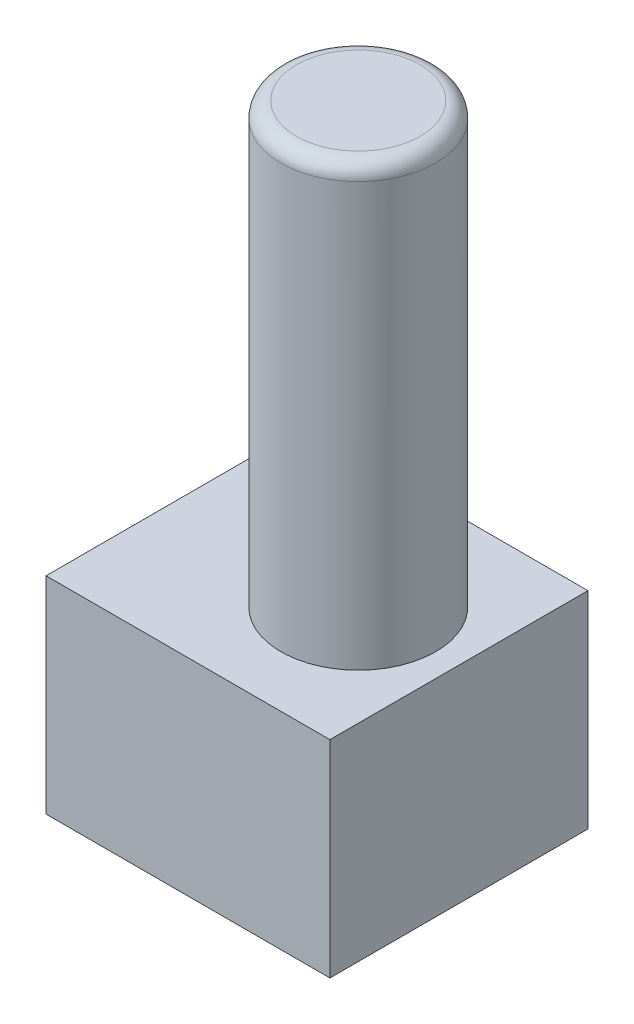
SolidWorks part; units mm, degrees
ref_plane "Front Plane" through (0, 0, 0) normal (0, 0, 1) x (1, 0, 0)
ref_plane "Top Plane" through (0, 0, 0) normal (0, 1, 0) x (1, 0, 0)
ref_plane "Right Plane" through (0, 0, 0) normal (1, 0, 0) x (0, 0, -1)
sketch "Sketch1" plane through (0, 0, 0) normal (0, 1, 0) x (1, 0, 0)
  line L1 (-5.5, -5) -> (5.5, -5)
  line L2 (-5.5, -5) -> (-5.5, 5)
  line L3 (-5.5, 5) -> (5.5, 5)
  line L4 (5.5, -5) -> (5.5, 5)
  line L5 (-5.5, -5) -> (5.5, 5) construction
  line L6 (-5.5, 5) -> (5.5, -5) construction
  circle A0 centre (1.6, 0) radius 3
  point P0 (0, 0)
  dimension "D3" = 6
  dimension "D4" = 3.9
  dimension "D1" = 11
  dimension "D2" = 10
extrude "Boss-Extrude1" add sketch "Sketch1" along normal blind 25 contours A0 region at (1.6, 0, 0)
extrude "Boss-Extrude2" add sketch "Sketch1<3>" along normal blind 8
sketch "Sketch1<3>" plane through (0, 0, 0) normal (0, 1, 0) x (1, 0, 0) same geometry as "Sketch1"
fillet "Fillet1" radius 0.6 1 edges at (1.6, 25, 3)
